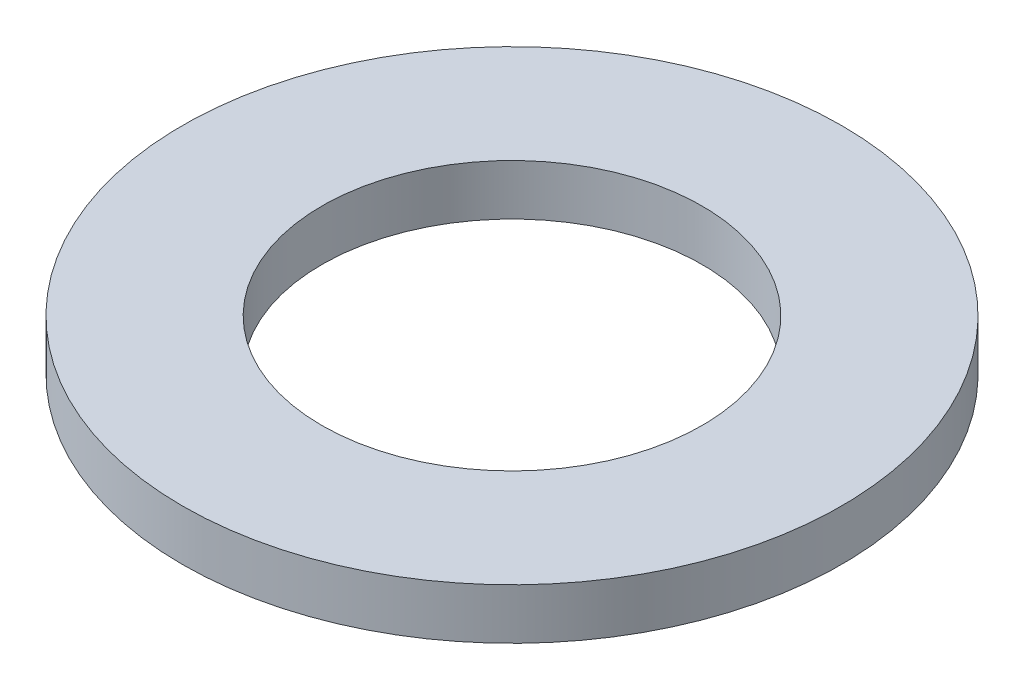
SolidWorks part; units mm, degrees
ref_plane "Front Plane" through (0, 0, 0) normal (0, 0, 1) x (1, 0, 0)
ref_plane "Top Plane" through (0, 0, 0) normal (0, 1, 0) x (1, 0, 0)
ref_plane "Right Plane" through (0, 0, 0) normal (1, 0, 0) x (0, 0, -1)
sketch "Sketch1" plane through (0, 0, 0) normal (0, 1, 0) x (1, 0, 0)
  circle A0 centre (0, 0) radius 65
  dimension "FLANGE_OD" = 130
extrude "Boss-Extrude1" add sketch "Sketch1" along normal blind 10
sketch "Sketch2" plane through (0, 0, 0) normal (0, 1, 0) x (1, 0, 0)
  circle A0 centre (0, 0) radius 37.5
  dimension "BORE_D" = 75
extrude "Cut-Extrude1" cut sketch "Sketch2" along normal through all
sketch "Sketch3" plane through (0, 10, 0) normal (0, 1, 0) x (1, 0, 0)
  circle A0 centre (0, 0) radius 25.2832 construction
  circle A1 centre (-25.2832, 0) radius 2.7792
  dimension "BOLT_D" = 5.5584
  dimension "BOLT_PCD" = 50.5663
extrude "Cut-Extrude2" cut sketch "Sketch3" against normal blind 8.048 rebuild error yes
pattern_circular "CirPattern1" count 8 over 360 rebuild error yes
